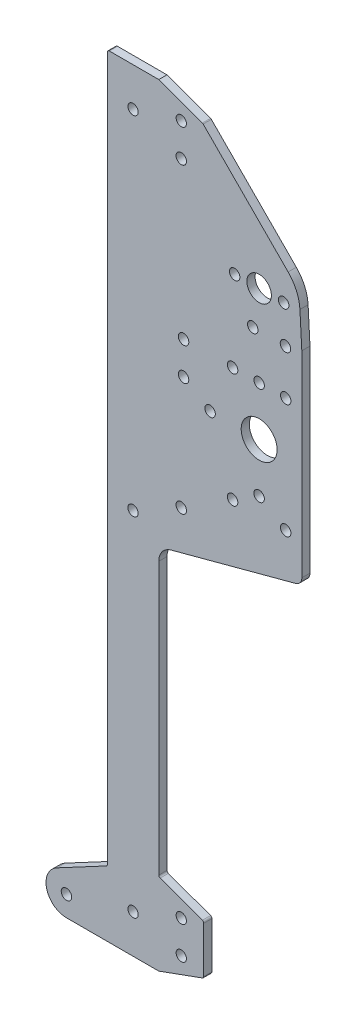
SolidWorks part; units mm, degrees
ref_plane "Front Plane" through (0, 0, 0) normal (0, 0, 1) x (1, 0, 0)
ref_plane "Top Plane" through (0, 0, 0) normal (0, 1, 0) x (1, 0, 0)
ref_plane "Right Plane" through (0, 0, 0) normal (1, 0, 0) x (0, 0, -1)
sketch "Sketch1" plane through (0, 0, 0) normal (0, 0, 1) x (1, 0, 0)
  line L1 (-10, 150) -> (10, 150)
  line L2 (-10, 150) -> (-10, -150)
  line L3 (-10, -150) -> (10, -150)
  line L4 (10, 150) -> (10, -150)
  line L5 (-10, 150) -> (10, -150) construction
  line L6 (-10, -150) -> (10, 150) construction
  point P0 (0, 0)
  dimension "D1" = 300
  dimension "20mm" = 20
extrude "Boss-Extrude1" add sketch "Sketch1" along normal blind 3.175
sketch "Sketch2" plane through (0, 0, 3.175) normal (0, 0, 1) x (1, 0, 0)
  line L0 (10, 150) -> (27.4625, 143.65)
  line L1 (27.4625, 143.65) -> (27.4625, 124.6)
  line L2 (27.4625, 124.6) -> (10, 118.25)
  line L3 (10, -150) -> (10, 150) construction
  line L4 (10, 118.25) -> (10, 150)
  line L5 (10, 150) -> (-10, 150) construction
  line L6 (-10, 0) -> (10, 0) construction
  line L7 (-10, 150) -> (-10, -150) construction
  line L8 (10, -118.25) -> (10, -150)
  line L9 (27.4625, -124.6) -> (10, -118.25)
  line L10 (27.4625, -143.65) -> (27.4625, -124.6)
  line L11 (10, -150) -> (27.4625, -143.65)
  line L12 (18.7312, 140.475) -> (18.7313, 127.775) construction
  line L13 (18.7313, -127.775) -> (18.7313, -140.475) construction
  circle A1 centre (18.7313, 127.775) radius 5 construction
  circle A2 centre (18.7312, 140.475) radius 2
  circle A4 centre (18.7313, -127.775) radius 5 construction
  circle A5 centre (18.7313, -127.775) radius 2
  circle A6 centre (18.7312, 134.125) radius 2 construction
  circle A7 centre (18.7313, -134.125) radius 2 construction
  circle A8 centre (18.7313, 127.775) radius 2.032
  circle A9 centre (18.7313, -140.475) radius 2
  point P3 (27.4625, 134.125)
  point P8 (10, 134.125)
  point P13 (18.7312, 121.425)
  point P31 (27.4625, -134.125)
  dimension "D3" = 4
  dimension "D4" = 10
  dimension "D7" = 4.064
  dimension "D1" = 17.4625
  dimension "2.5" = 31.75
  dimension "D2" = 19.05
  dimension "D5" = 9.525
  dimension "D6" = 9.525
  dimension "D8" = 12.7
extrude "Boss-Extrude2" add sketch "Sketch2" against normal up to surface (3.175 mm away) up to face at (0, 0, 0)
sketch "Sketch4" plane through (0, 0, 3.175) normal (0, 0, 1) x (1, 0, 0)
  line L0 (0, 150) -> (0, 135) construction
  line L2 (0, 135) -> (0, 0) construction
  line L3 (0, 0) -> (0, -135) construction
  line L4 (0, -135) -> (0, -150) construction
  line L6 (10, 150) -> (-10, 150) construction
  line L7 (-10, -150) -> (10, -150) construction
  circle A0 centre (0, -135) radius 2
  circle A1 centre (0, 0) radius 2
  circle A2 centre (0, 135) radius 2
  dimension "D4" = 4
  dimension "D1" = 15
  dimension "D2" = 135
  dimension "D3" = 135
extrude "Cut-Extrude1" cut sketch "Sketch4" against normal through all
sketch "Sketch5" plane through (0, 0, 3.175) normal (0, 0, 1) x (1, 0, 0)
  line L0 (-10, 111.9) -> (-41.75, 118.25)
  line L1 (-10, 150) -> (-10, -150) construction
  line L2 (-41.75, 118.25) -> (-41.75, 137.3)
  line L3 (-41.75, 137.3) -> (-10, 137.3)
  line L4 (-10, 137.3) -> (-10, 111.9)
  line L5 (10, 150) -> (-10, 150) construction
  line L6 (-41.75, 133.3313) -> (-37.7813, 133.3313) construction
  line L7 (-13.9688, 133.3313) -> (-10, 133.3313) construction
  line L8 (-10, -150) -> (-25.875, -150)
  line L9 (-29.6103, -135.0588) -> (-10, -124.6)
  line L10 (-10, -124.6) -> (-10, -150)
  circle A0 centre (-13.9688, 133.3313) radius 2.032
  circle A1 centre (-13.9688, 122.2188) radius 2.032
  circle A2 centre (-37.7813, 133.3313) radius 2.032
  circle A3 centre (-37.7813, 122.2188) radius 2.032
  arc A4 (-25.875, -150) -> (-29.6103, -135.0588) centre (-25.875, -142.0625) cw
  circle A5 centre (-25.875, -142.0625) radius 2.032
  point P24 (-25.875, 137.3)
  dimension "D5" = 4.064
  dimension "D9" = 4.064
  dimension "D10" = 7.9375
  dimension "D1" = 12.7
  dimension "D2" = 19.05
  dimension "D3" = 25.4
  dimension "D4" = 31.75
  dimension "D6" = 11.1125
  dimension "D7" = 23.8125
  dimension "D8" = 3.9688
  dimension "D11" = 25.4
extrude "Boss-Extrude3" [suppressed] add sketch "Sketch5" against normal up to surface (1.5875 mm away) up to face at (2, -135, 0)
fillet "Fillet3" [suppressed] radius 1.5875
sketch "Sketch6" plane through (0, 0, 3.175) normal (0, 0, 1) x (1, 0, 0)
  line L0 (-10, -124.6) -> (-10, -150) construction
  line L1 (-10, -150) -> (-25.875, -150) construction
  line L2 (-29.6103, -135.0588) -> (-10, -124.6) construction
  line L3 (-10, -124.6) -> (-10, -150)
  line L4 (-10, -150) -> (-25.875, -150)
  line L5 (-29.6103, -135.0588) -> (-10, -124.6)
  circle A0 centre (-25.875, -142.0625) radius 2.032 construction
  arc A1 (-29.6103, -135.0588) -> (-25.875, -150) centre (-25.875, -142.0625) ccw construction
  circle A2 centre (-25.875, -142.0625) radius 2.032
  arc A3 (-29.6103, -135.0588) -> (-25.875, -150) centre (-25.875, -142.0625) ccw
extrude "Boss-Extrude4" add sketch "Sketch6" against normal up to vertex (3.175 mm away) up to point (-10, -150, 0)
fillet "Fillet4" radius 0.7937 8 edges at (10, 118.25, 1.5875) (27.4625, 124.6, 1.5875) (-10, 150, 1.5875) (27.4625, 143.65, 1.5875) (-10, -124.6, 1.5875) (10, -118.25, 1.5875) (27.4625, -124.6, 1.5875) (27.4625, -143.65, 1.5875)
fillet "Fillet5" [suppressed] radius 1.5875
sketch "Sketch7" plane through (0, 0, 0) normal (0, 0, -1) x (-1, 0, 0)
  line L0 (-27.1212, 143.7462) -> (-65.2212, 117.3147)
  line L1 (-65.5625, 116.6625) -> (-65.5625, 10.1095)
  line L2 (-63.2093, 7.0427) -> (-10, -7.2147)
  line L4 (-10, -7.2147) -> (-10, 117.694)
  line L5 (-27.4625, 143.094) -> (-27.4625, 125.156) construction
  line L6 (-26.94, 124.41) -> (-10.5225, 118.44) construction
  line L7 (-27.4625, 143.094) -> (-27.4625, 125.156)
  line L8 (-26.94, 124.41) -> (-10.5225, 118.44)
  line L9 (-10, 150) -> (9.2063, 150) construction
  line L10 (-10, 150) -> (9.2063, 150) construction
  line L11 (-48.989, 45.225) -> (-48.989, 48.4) construction
  line L12 (-38.6703, 23) -> (-59.3078, 23) construction
  line L13 (-38.6703, 23) -> (-38.6703, 67.45) construction
  line L14 (-38.6703, 67.45) -> (-59.3078, 67.45) construction
  line L15 (-59.3078, 23) -> (-59.3078, 67.45) construction
  line L16 (-38.6703, 23) -> (-59.3078, 67.45) construction
  line L17 (-38.6703, 67.45) -> (-59.3078, 23) construction
  line L18 (-48.989, 99.2) -> (-48.989, 48.4) construction
  line L19 (-10, -117.694) -> (-10, 117.694) construction
  arc A0 (-65.2212, 117.3147) -> (-65.5625, 116.6625) centre (-64.7688, 116.6625) ccw
  arc A1 (-65.5625, 10.1095) -> (-63.2093, 7.0427) centre (-62.3875, 10.1095) ccw
  arc A2 (-26.94, 143.84) -> (-27.4625, 143.094) centre (-26.6688, 143.094) ccw construction
  arc A3 (-27.4625, 125.156) -> (-26.94, 124.41) centre (-26.6688, 125.156) ccw construction
  arc A4 (-10, 117.694) -> (-10.5225, 118.44) centre (-10.7937, 117.694) ccw construction
  arc A5 (-27.1212, 143.7462) -> (-27.4625, 143.094) centre (-26.6688, 143.094) ccw
  arc A6 (-27.4625, 125.156) -> (-26.94, 124.41) centre (-26.6688, 125.156) ccw
  arc A7 (-10, 117.694) -> (-10.5225, 118.44) centre (-10.7937, 117.694) ccw
  arc A8 (10, 149.2063) -> (9.2063, 150) centre (9.2063, 149.2063) ccw construction
  circle A9 centre (-48.989, 99.2) radius 4.7625
  circle A10 centre (-48.989, 48.4) radius 6.985
  circle A11 centre (-59.3078, 67.45) radius 2.032
  circle A12 centre (-59.3078, 23) radius 2.032
  circle A13 centre (-38.6703, 23) radius 2.032
  circle A14 centre (-38.6703, 67.45) radius 2.032
  circle A15 centre (-18.7312, 10.3) radius 2.032
  point P32 (-48.989, 45.225)
  point P42 (0, 0)
  dimension "D4" = 9.525
  dimension "D6" = 13.97
  dimension "D11" = 4.064
  dimension "D15" = 3.175
  dimension "D1" = 38.1
  dimension "D2" = 106.553
  dimension "D3" = 16.5735
  dimension "D5" = 50.8
  dimension "D7" = 3.175
  dimension "D8" = 44.45
  dimension "D9" = 50.8
  dimension "D10" = 20.6375
  dimension "D12" = 75
  dimension "D13" = 139.7
  dimension "D14" = 33.3375
extrude "Boss-Extrude5" add sketch "Sketch7" against normal up to surface (3.175 mm away) up to face at (2, -135, 3.175)
sketch "Sketch8" plane through (0, 0, 3.175) normal (0, 0, 1) x (1, 0, 0)
  line L0 (48.989, 48.4) -> (48.989, 67.45) construction
  line L1 (48.989, 48.4) -> (29.939, 48.4) construction
  line L2 (48.989, 48.4) -> (48.989, 29.35) construction
  line L3 (48.989, 99.2) -> (58.514, 99.2) construction
  line L4 (48.989, 99.2) -> (39.464, 99.2) construction
  line L5 (19.6203, 67.45) -> (19.6203, 54.75) construction
  circle A0 centre (48.989, 67.45) radius 2.032
  circle A1 centre (29.939, 48.4) radius 2.032
  circle A2 centre (48.989, 29.35) radius 2.032
  circle A3 centre (59.3078, 67.45) radius 2.032 construction
  circle A4 centre (58.514, 99.2) radius 2.032
  circle A5 centre (39.464, 99.2) radius 2.032
  circle A6 centre (19.6203, 54.75) radius 2.032
  circle A7 centre (19.6203, 67.45) radius 2.032
  dimension "D2" = 9.525
  dimension "D1" = 19.05
  dimension "D3" = 12.7
  dimension "D4" = 6.35
  dimension "D5" = 10.3187
extrude "Cut-Extrude2" cut sketch "Sketch8" against normal through all
sketch "Sketch9" plane through (0, 0, 0) normal (0, 0, -1) x (-1, 0, 0)
  line L0 (-27.2321, 143.6532) -> (-60.2559, 110.3836)
  line L2 (-65.5625, 86.5) -> (-64.8416, 100.0438)
  line L3 (-65.5625, 86.5) -> (-65.5625, 116.6625)
  line L4 (-27.1212, 143.7462) -> (-65.2212, 117.3147) construction
  line L5 (-27.1212, 143.7462) -> (-65.2212, 117.3147)
  line L6 (-65.5625, 116.6625) -> (-65.5625, 10.1095) construction
  arc A0 (-26.94, 143.84) -> (-27.1212, 143.7462) centre (-26.6688, 143.094) ccw construction
  arc A1 (-27.1212, 143.7462) -> (-27.2321, 143.6532) centre (-26.6688, 143.094) ccw
  arc A2 (-60.2559, 110.3836) -> (-64.8416, 100.0438) centre (-48.989, 99.2) ccw
  arc A4 (-65.2212, 117.3147) -> (-65.5625, 116.6625) centre (-64.7688, 116.6625) ccw construction
  arc A5 (-65.2212, 117.3147) -> (-65.5625, 116.6625) centre (-64.7688, 116.6625) ccw
  circle A6 centre (-59.3078, 67.45) radius 2.032 construction
  dimension "D1" = 15.875
  dimension "D2" = 19.05
extrude "Cut-Extrude3" cut sketch "Sketch9" against normal through all
sketch "Sketch10" plane through (0, 0, 0) normal (0, 0, -1) x (-1, 0, 0)
  line L0 (-59.2125, 84.9125) -> (-46.5125, 84.9125) construction
  line L1 (-65.5625, 86.5) -> (-65.5625, 10.1095) construction
  circle A0 centre (-59.2125, 84.9125) radius 2.032
  circle A1 centre (-46.5125, 84.9125) radius 2.032
  circle A2 centre (-59.3078, 67.45) radius 2.032 construction
  point P6 (-48.989, 67.45)
  dimension "D1" = 12.7
  dimension "D2" = 17.4625
  dimension "D3" = 6.35
extrude "Cut-Extrude4" cut sketch "Sketch10" against normal through all
fillet "Fillet6" radius 6.35 1 edges at (10, -7.2147, 1.5875)
